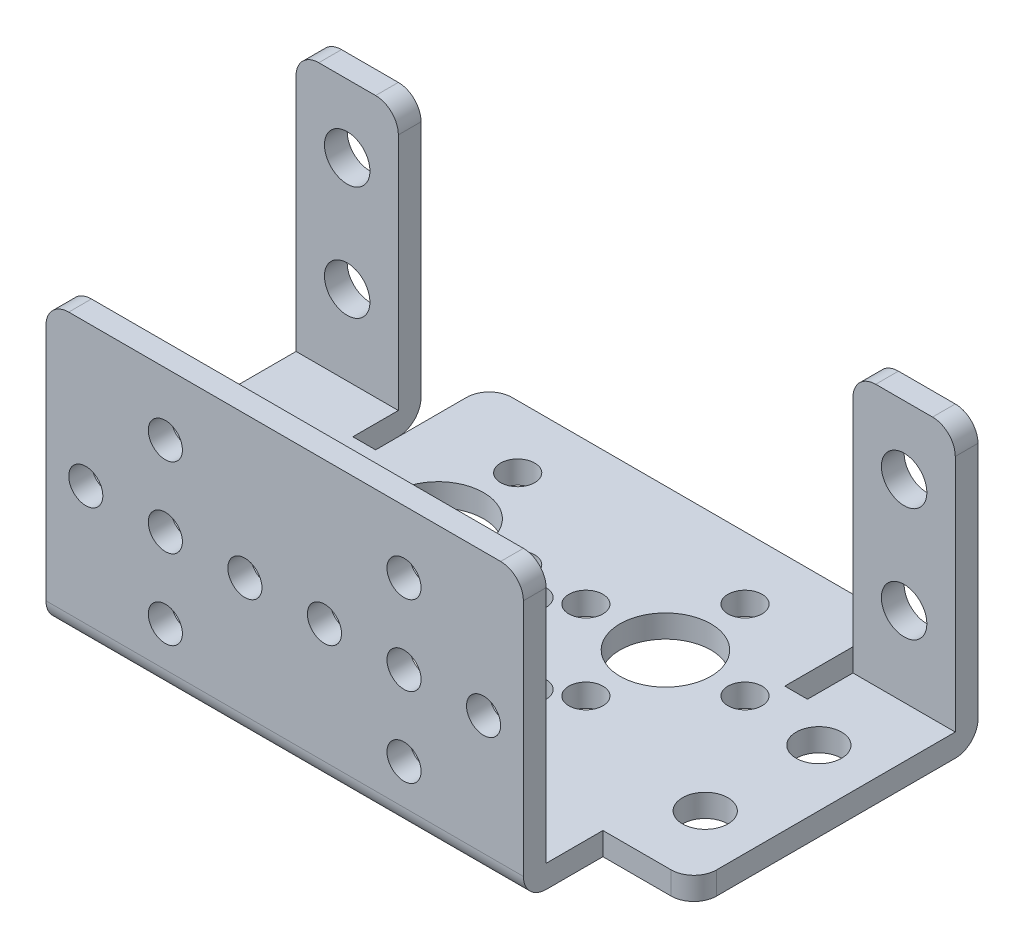
SolidWorks part; units mm, degrees
ref_plane "Front Plane" through (0, 0, 0) normal (0, 0, 1) x (1, 0, 0)
ref_plane "Top Plane" through (0, 0, 0) normal (0, 1, 0) x (1, 0, 0)
ref_plane "Right Plane" through (0, 0, 0) normal (1, 0, 0) x (0, 0, -1)
sketch "Sketch1" plane through (0, 0, 0) normal (0, 0, 1) x (1, 0, 0)
  line L1 (0, 0) -> (42, 0)
  line L2 (0, 0) -> (0, 25)
  line L3 (0, 25) -> (42, 25)
  line L4 (42, 0) -> (42, 25)
  circle A0 centre (10.5, 12.5) radius 1.5
  circle A1 centre (10.5, 19.5) radius 1.5
  circle A2 centre (17.5, 12.5) radius 1.5
  circle A3 centre (3.5, 12.5) radius 1.5
  circle A4 centre (10.5, 5.5) radius 1.5
  circle A5 centre (31.5, 12.5) radius 1.5
  circle A6 centre (38.5, 12.5) radius 1.5
  circle A7 centre (31.5, 19.5) radius 1.5
  circle A8 centre (24.5, 12.5) radius 1.5
  circle A9 centre (31.5, 5.5) radius 1.5
  dimension "D3" = 3
  dimension "D1" = 42
  dimension "D2" = 25
  dimension "D4" = 7
  dimension "D5" = 7
  dimension "D6" = 7
  dimension "D7" = 7
  dimension "D8" = 7
  dimension "D9" = 7
  dimension "D10" = 12.5
  dimension "D11" = 10.5
  dimension "D12" = 10.5
extrude "Boss-Extrude1" add sketch "Sketch1" against normal blind 2
sketch "Sketch2" plane through (0, 0, 0) normal (0, -1, 0) x (1, 0, 0)
  line L0 (0, -32) -> (0, -36)
  line L1 (0, 0) -> (42, 0)
  line L2 (0, 0) -> (0, -7)
  line L3 (0, -36) -> (42, -36)
  line L4 (42, 0) -> (42, -7)
  line L5 (-6, -7) -> (0, -7)
  line L6 (-8, -9) -> (-8, -32)
  line L7 (-8, -32) -> (0, -32)
  line L8 (50, -9) -> (50, -32)
  line L9 (42, -7) -> (48, -7)
  line L10 (42, -32) -> (50, -32)
  line L11 (42, -32) -> (42, -36)
  line L12 (21, -2) -> (21, -36) construction
  line L13 (0, -2) -> (42, -2) construction
  line L14 (19.5, -23.5) -> (21, -23.5) construction
  line L15 (22.5, -23.5) -> (21, -23.5) construction
  circle A0 centre (45, -13) radius 2
  circle A1 centre (45, -23) radius 2
  circle A2 centre (-3, -13) radius 2
  circle A3 centre (-3, -23) radius 2
  arc A4 (-6, -7) -> (-8, -9) centre (-6, -9) ccw
  arc A5 (48, -7) -> (50, -9) centre (48, -9) cw
  circle A6 centre (11, -23.5) radius 4
  circle A7 centre (31, -23.5) radius 4
  circle A8 centre (21, -14.5) radius 4
  circle A9 centre (11, -16.5) radius 1.5
  circle A10 centre (11, -30.5) radius 1.5
  circle A11 centre (18, -23.5) radius 1.5
  circle A12 centre (4, -23.5) radius 1.5
  circle A13 centre (31, -30.5) radius 1.5
  circle A14 centre (24, -23.5) radius 1.5
  circle A15 centre (31, -16.5) radius 1.5
  circle A16 centre (38, -23.5) radius 1.5
  circle A17 centre (21, -21.5) radius 1.5
  circle A18 centre (21, -7.5) radius 1.5
  circle A19 centre (28, -14.5) radius 1.5
  circle A20 centre (14, -14.5) radius 1.5
  point P24 (-8, -7)
  point P27 (50, -7)
  dimension "D6" = 2
  dimension "D7" = 4
  dimension "D8" = 10
  dimension "D10" = 5
  dimension "D11" = 5
  dimension "D12" = 8
  dimension "D13" = 14.5
  dimension "D14" = 12.5
  dimension "D15" = 3
  dimension "D1" = 36
  dimension "D2" = 25
  dimension "D3" = 7
  dimension "D4" = 58
  dimension "D5" = 8
  dimension "D9" = 6
  dimension "D16" = 7
  dimension "D17" = 7
  dimension "D18" = 7
  dimension "D19" = 7
  dimension "D20" = 7
  dimension "D21" = 7
  dimension "D22" = 7
  dimension "D23" = 7
  dimension "D24" = 7
  dimension "D25" = 7
  dimension "D26" = 20
  dimension "D27" = 7
extrude "Boss-Extrude2" add sketch "Sketch2" against normal blind 2
sketch "Sketch3" plane through (0, 0, 0) normal (0, -1, 0) x (1, 0, 0)
  line L0 (39, -36) -> (39, -26)
  line L1 (0, -36) -> (42, -36) construction
  line L2 (39, -26) -> (41, -26)
  line L3 (41, -26) -> (41, -32)
  line L4 (41, -32) -> (42, -32)
  line L17 (42, 0) -> (0, 0)
  line L18 (0, 0) -> (0, -7)
  line L19 (0, -7) -> (-6, -7)
  line L20 (-8, -9) -> (-8, -32)
  line L21 (-8, -32) -> (0, -32)
  line L22 (0, -32) -> (0, -36)
  line L23 (0, -36) -> (42, -36)
  line L24 (42, -36) -> (42, -32)
  line L25 (42, -32) -> (50, -32)
  line L26 (50, -32) -> (50, -9)
  line L27 (48, -7) -> (42, -7)
  line L28 (42, -7) -> (42, 0)
  line L35 (39, -36) -> (42, -36)
  line L36 (42, -36) -> (42, -32)
  arc A2 (-6, -7) -> (-8, -9) centre (-6, -9) ccw
  arc A3 (50, -9) -> (48, -7) centre (48, -9) ccw
  dimension "D1" = 10
  dimension "D2" = 2
  dimension "D3" = 1
  dimension "D4" = 0
extrude "Cut-Extrude1" cut sketch "Sketch3" against normal blind 2
ref_plane "Plane1" through (21, 0, 0) normal (1, 0, 0) x (0, 0, -1)
mirror "Mirror1" about plane through (21, 0, 0) normal (1, 0, 0) of "Cut-Extrude1"
fillet "Fillet1" radius 2 1 edges at (3, 1, -36)
fillet "Fillet2" radius 2 1 edges at (39, 1, -36)
fillet "Fillet3" radius 2 1 edges at (21, 0, 0)
fillet "Fillet4" radius 2 1 edges at (42, 25, -1)
fillet "Fillet5" radius 2 1 edges at (0, 25, -1)
sketch "Sketch4" plane through (0, 0, -32) normal (0, 0, -1) x (-1, 0, 0)
  line L1 (8, 0) -> (-1, 0)
  line L2 (8, 0) -> (8, 23)
  line L3 (6, 25) -> (1, 25)
  line L4 (-1, 0) -> (-1, 23)
  arc A0 (8, 23) -> (6, 25) centre (6, 23) ccw
  arc A1 (1, 25) -> (-1, 23) centre (1, 23) ccw
  dimension "D1" = 2
  dimension "D2" = 9
  dimension "D3" = 25
extrude "Boss-Extrude3" add sketch "Sketch4" against normal blind 2
mirror "Mirror2" about plane through (21, 0, 0) normal (1, 0, 0) of "Boss-Extrude3"
fillet "Fillet6" radius 2 1 edges at (45.5, 0, -32)
fillet "Fillet7" radius 2 1 edges at (-3.5, 0, -32)
sketch "Sketch5" plane through (0, 0, -32) normal (0, 0, -1) x (-1, 0, 0)
  line L0 (3.5, 25) -> (3.5, 0) construction
  line L1 (6, 25) -> (1, 25) construction
  circle A0 centre (3.5, 19) radius 2
  circle A1 centre (3.5, 9) radius 2
  dimension "D2" = 4
  dimension "D1" = 10
  dimension "D3" = 6
extrude "Cut-Extrude2" cut sketch "Sketch5" against normal blind 2
mirror "Mirror3" about plane through (21, 0, 0) normal (1, 0, 0) of "Cut-Extrude2"
